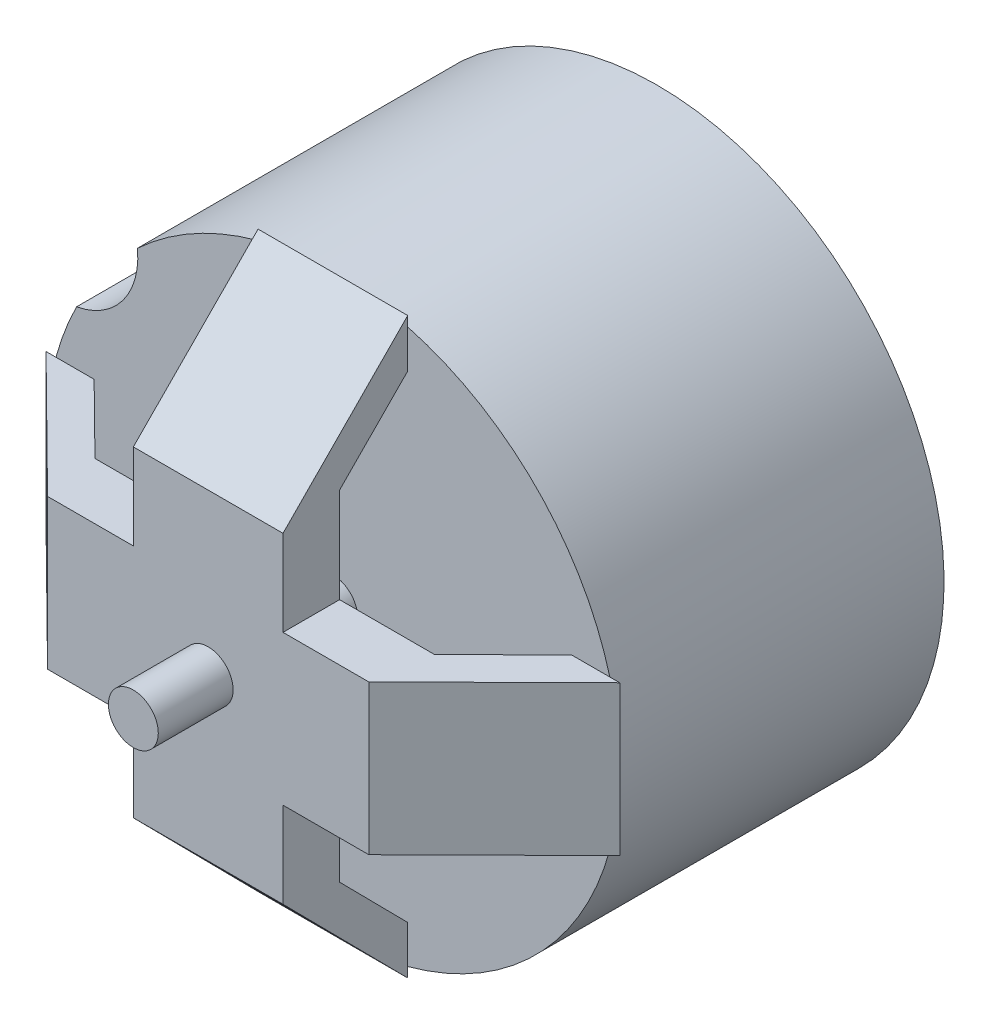
SolidWorks part; units mm, degrees
ref_plane "Front" through (0, 0, 0) normal (0, 0, 1) x (1, 0, 0)
ref_plane "Top" through (0, 0, 0) normal (0, 1, 0) x (1, 0, 0)
ref_plane "Right" through (0, 0, 0) normal (1, 0, 0) x (0, 0, -1)
sketch "Çizim1" plane through (0, 0, 0) normal (0, 0, 1) x (1, 0, 0)
  line L0 (-8, 0) -> (0, 6) construction
  line L1 (0, 0) -> (-10.8199, 8.1149) construction
  circle A0 centre (0, 0) radius 11.5
  circle A1 centre (0, 0) radius 1.5
  circle A2 centre (0, 0) radius 6 construction
  circle A3 centre (0, 0) radius 8 construction
  circle A4 centre (0, 6) radius 1.5
  circle A5 centre (0, -6) radius 1.5
  circle A6 centre (-8, 0) radius 1.5
  circle A7 centre (8, 0) radius 1.5
  circle A8 centre (0, 0) radius 4
  circle A9 centre (0, 0) radius 2.5
  circle A10 centre (-10.8199, 8.1149) radius 3
  point P19 (-4, 3)
  dimension "D1" = 23
  dimension "D2" = 3
  dimension "D3" = 16
  dimension "D4" = 12
  dimension "D5" = 3
  dimension "D6" = 3
  dimension "D7" = 3
  dimension "D8" = 3
extrude "Yükseklik-Ekstrüzyon1" add sketch "Çizim1" along normal blind 13 contours A0 A8 A7 A6 A5 A4 | A8 A9 | A9 A1 | A4 | A6 | A7 | A5 | A1 region at (-2.579, -10.8731, 0) region at (0, 0, 0) region at (0, 6, 0) region at (0, -6, 0) region at (-8, 0, 0) region at (8, 0, 0) region at (-3.8869, 0, 0) region at (-2.4293, 0, 0)
extrude "Yükseklik-Ekstrüzyon2" add sketch "Çizim1<2>" against normal blind 2 contours A1
sketch "Çizim1<2>" plane through (0, 0, 0) normal (0, 0, 1) x (1, 0, 0) same geometry as "Çizim1"
extrude "Yükseklik-Ekstrüzyon3" add sketch "Çizim1<4>" against normal blind 0.8 contours A9 A1 region at (-2.4293, 0, 0)
sketch "Çizim1<4>" plane through (0, 0, 0) normal (0, 0, 1) x (1, 0, 0) same geometry as "Çizim1"
sketch "Çizim5" plane through (0, 0, 0) normal (1, 0, 0) x (0, 0, -1)
  line L0 (-13, 11.5) -> (-18, 6.4392)
  line L1 (-18, 6.4392) -> (-18, 0)
  line L2 (-18, 0) -> (-15.7324, 0)
  line L3 (-15.7324, 0) -> (-15.7324, 6.8061)
  line L4 (-15.7324, 6.8061) -> (-13, 9.5718)
  line L5 (-13, 11.5) -> (-13, -11.5) construction
  line L6 (-13, 9.5718) -> (-13, 11.5)
  point P11 (-18, 0)
  dimension "D1" = 5
extrude "Yükseklik-Ekstrüzyon4" add sketch "Çizim5" along normal blind 3 and the other way blind 3
sketch "Çizim6" plane through (0, 0, 0) normal (0, -1, 0) x (-1, 0, 0)
  line L0 (0, -18) -> (0, -15.7324)
  line L1 (3, -15.7324) -> (-3, -15.7324) construction
pattern_circular "Dairesel Kaplama1" count 4 over 360 about axis through (0, 0, 13) along (0, 0, 1) of "Yükseklik-Ekstrüzyon4", "Yükseklik-Ekstrüzyon1"
sketch "Çizim7" plane through (0, 0, 18) normal (0, 0, 1) x (1, 0, 0)
  circle A0 centre (0, 0) radius 1
  dimension "D1" = 2
extrude "Yükseklik-Ekstrüzyon5" add sketch "Çizim7" along normal blind 3 and the other way blind 8.2
extrude "Kes-Ekstrüzyon2" cut sketch "Çizim1<6>" along normal blind 15 contours A0 A10 region at (-8.8551, 6.6413, 0)
sketch "Çizim1<6>" plane through (0, 0, 0) normal (0, 0, 1) x (1, 0, 0) same geometry as "Çizim1"
extrude "Kes-Ekstrüzyon3" cut sketch "Çizim1<7>" along normal blind 3 contours A6 | A4 | A7 | A5 region at (0, 6, 0) region at (0, -6, 0) region at (-8, 0, 0) region at (8, 0, 0)
sketch "Çizim1<7>" plane through (0, 0, 0) normal (0, 0, 1) x (1, 0, 0) same geometry as "Çizim1"
extrude "Kes-Ekstrüzyon4" cut sketch "Çizim1<8>" along normal blind 0.2 contours A8 A9 region at (-3.8869, 0, 0)
sketch "Çizim1<8>" plane through (0, 0, 0) normal (0, 0, 1) x (1, 0, 0) same geometry as "Çizim1"
